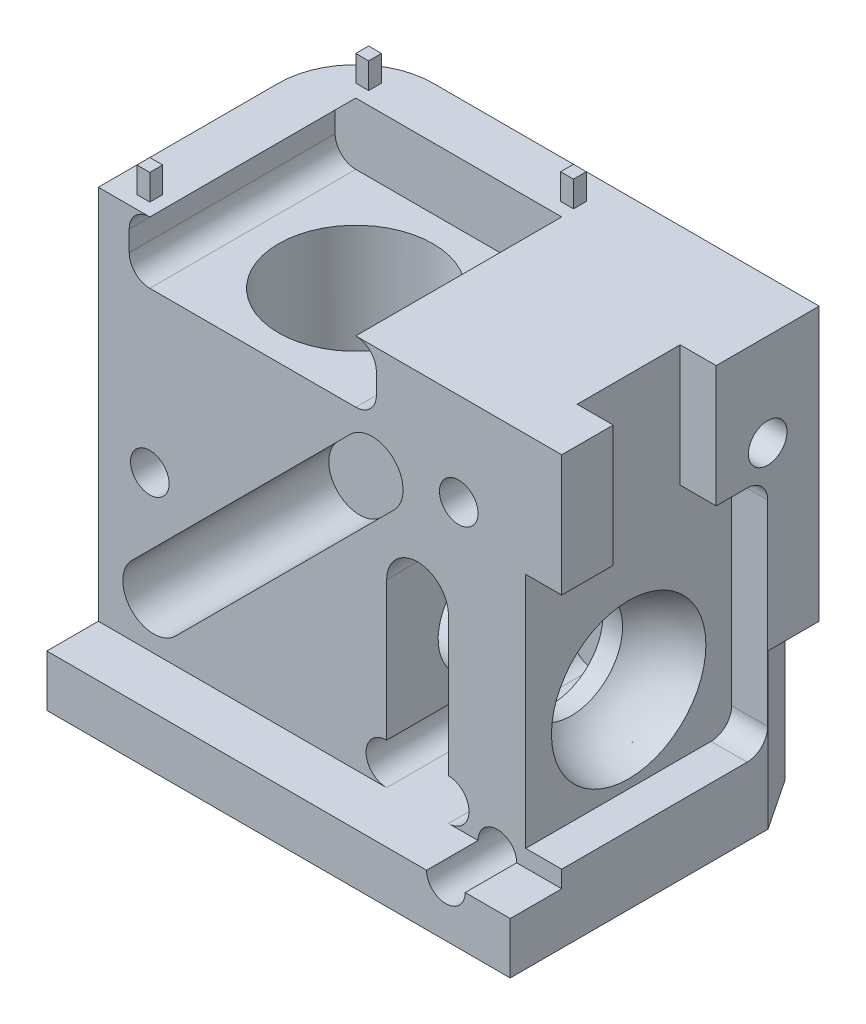
SolidWorks part; units mm, degrees
ref_plane "Front Plane" through (0, 0, 0) normal (0, 0, 1) x (1, 0, 0)
ref_plane "Top Plane" through (0, 0, 0) normal (0, 1, 0) x (1, 0, 0)
ref_plane "Right Plane" through (0, 0, 0) normal (1, 0, 0) x (0, 0, -1)
sketch "Sketch1" plane through (0, 0, 0) normal (0, 1, 0) x (1, 0, 0)
  line L1 (4.5, 3) -> (-4.5, 3)
  line L2 (4.5, 3) -> (4.5, -3)
  line L3 (4.5, -3) -> (-4.5, -3)
  line L4 (-4.5, 3) -> (-4.5, -3)
  line L5 (4.5, 3) -> (-4.5, -3) construction
  line L6 (4.5, -3) -> (-4.5, 3) construction
  point P0 (0, 0)
  dimension "D1" = 6
  dimension "D2" = 9
extrude "Main Body Ext" add sketch "Sketch1" along normal blind 8.3
sketch "Sketch8" plane through (0, 8.3, 0) normal (0, 1, 0) x (1, 0, 0)
  line L0 (0.25, 3) -> (1.5, 1.75)
  line L1 (0.25, 3) -> (-4.5, 3)
  line L2 (1.5, 1.75) -> (1.5, -3)
  line L3 (1.5, -3) -> (-4.5, -3)
  line L4 (-4.5, 3) -> (-4.5, -3)
  line L5 (0.875, 2.375) -> (-4.5, -3) construction
  line L6 (1.5, -3) -> (-4.5, 3) construction
  line L7 (-4.5, 3) -> (-4.5, -3) construction
  line L8 (0, 0) -> (-1.5, 0) construction
  point P0 (-1.5, 0)
  dimension "D1" = 6
  dimension "D2" = 6
  dimension "D3" = 1.25
  dimension "D4" = 3
extrude "Emission Path Ext" add sketch "Sketch8" along normal blind 9
sketch "Sketch3" plane through (0, 0, 0) normal (0, -1, 0) x (1, 0, 0)
  line L0 (-4.5, -3) -> (-4.5, 3) construction
  line L1 (0, 0) -> (-1.5, 0) construction
  circle A0 centre (-1.5, 0) radius 1.25
  dimension "D1" = 3
  dimension "D2" = 2.5
extrude "Emission and Grin Cut" cut sketch "Sketch3" against normal through all
sketch "Sketch4" plane through (4.5, 0, 0) normal (1, 0, 0) x (0, 0, -1)
  line L1 (-3, 0) -> (3, 0) construction
  circle A0 centre (0, 3) radius 1
  dimension "D1" = 2
  dimension "D2" = 3
extrude "Drum Lens Cut" cut sketch "Sketch4" against normal offset from surface (7 mm away) 2 up to face at (-4.5, 8.65, 0)
sketch "Sketch5" plane through (0, 0, 3) normal (0, 0, 1) x (1, 0, 0)
  line L0 (-4.5, 0) -> (4.5, 0) construction
  line L1 (4.5, 8.3) -> (-4.5, 8.3)
  line L2 (4.5, 8.3) -> (4.5, 1)
  line L3 (4.5, 1) -> (-4.5, 1)
  line L4 (-4.5, 8.3) -> (-4.5, 1)
  line L5 (4.5, 8.3) -> (-4.5, 1) construction
  line L6 (4.5, 1) -> (-4.5, 8.3) construction
  line L7 (1.5, 8.3) -> (4.5, 8.3) construction
  line L9 (4.5, 8.3) -> (4.5, 0) construction
  line L10 (-4.5, 17.3) -> (-4.5, 0) construction
  point P0 (0, 4.65)
  dimension "D1" = 1
extrude "FilterSet Cut1" cut sketch "Sketch5" against normal blind 1
sketch "Sketch6" plane through (0, 0, 2) normal (0, 0, 1) x (1, 0, 0)
  line L0 (2.3, 4.5) -> (2.3, 1.8)
  line L1 (1.1, 4.5) -> (2.3, 4.5) construction
  line L2 (2.3, 1) -> (1.1, 1)
  line L3 (-4.5, 1) -> (4.5, 1) construction
  line L4 (-4.5, 8.3) -> (-4.5, 1) construction
  line L5 (-3.9, 7.9) -> (-3.9, 7.5)
  line L6 (1.1, 4.5) -> (1.1, 1.8)
  line L7 (1.5, 8.3) -> (-4.5, 8.3) construction
  line L8 (0.9, 7.9) -> (0.9, 7.5)
  line L9 (-3, 1.5) -> (-3, 1) construction
  line L10 (0.5, 8.3) -> (-3.5, 8.3)
  line L11 (-1.5, 3) -> (-1.5, 1) construction
  line L12 (-1.5, 3) -> (0.4851, 3) construction
  line L13 (0.5, 7.1) -> (-3.5, 7.1)
  line L15 (0.5, 8.3) -> (-3.5, 7.1) construction
  line L16 (0.5, 7.1) -> (-3.5, 8.3) construction
  line L17 (1.1, 1.8) -> (2.3, 1.8) construction
  line L18 (0.3941, 6.5912) -> (-3.8485, 2.3485)
  line L19 (4.5, 1) -> (4.5, 8.3) construction
  line L20 (1.2426, 5.7426) -> (-3, 1.5)
  line L21 (0.3941, 6.5912) -> (-3, 1.5) construction
  line L22 (-3.8485, 2.3485) -> (1.2426, 5.7426) construction
  line L33 (0.5, 8.3) -> (1.102, 8.3) construction
  line L34 (1.102, 8.3) -> (1.102, 7.1) construction
  line L35 (1.102, 7.1) -> (0.5, 7.1) construction
  line L36 (-3.5, 7.1) -> (-4.098, 7.1) construction
  line L37 (-4.098, 7.1) -> (-4.098, 8.3) construction
  line L38 (-4.098, 8.3) -> (-3.5, 8.3) construction
  line L39 (-3.5, 8.3) -> (-2.7284, 6.992) construction
  arc A0 (0.5, 8.3) -> (0.9, 7.9) centre (0.5, 7.9) cw
  arc A1 (1.1, 4.5) -> (2.3, 4.5) centre (1.7, 4.5) cw
  arc A2 (-3.5, 8.3) -> (-3.9, 7.9) centre (-3.5, 7.9) ccw
  arc A3 (0.3941, 6.5912) -> (1.2426, 5.7426) centre (0.8184, 6.1669) cw
  arc A4 (1.1, 1) -> (1.1, 1.8) centre (1.1, 1.4) cw
  arc A5 (-3.8485, 2.3485) -> (-3, 1.5) centre (-3.4243, 1.9243) ccw
  arc A6 (2.3, 1) -> (2.3, 1.8) centre (2.3, 1.4) ccw
  arc A7 (-3.5, 7.1) -> (-3.9, 7.5) centre (-3.5, 7.5) cw
  arc A8 (0.5, 7.1) -> (0.9, 7.5) centre (0.5, 7.5) ccw
  point P5 (-1.5, 7.7)
  point P10 (-1.3029, 4.0456)
  dimension "D10" = 0.5
  dimension "D5" = 2.2
  dimension "D8" = 0.4
  dimension "D11" = 0.4
  dimension "D12" = 0.4
  dimension "D1" = 1.2
  dimension "D2" = 45
  dimension "D3" = 3.5
  dimension "D4" = 1.2
  dimension "D6" = 2
  dimension "D7" = 4
  dimension "D9" = 3
  dimension "D13" = 1.2
  dimension "D14" = 3
  dimension "D15" = 6
extrude "FilterSet Cut2" cut sketch "Sketch6" against normal offset from surface (4 mm away) 1 up to face at (0.4375, 9.2833, -3)
sketch "Sketch10" plane through (0, 17.3, 0) normal (0, 1, 0) x (1, 0, 0)
  line L0 (-1.5, 0) -> (-1.5, -3) construction
  line L1 (-4.5, -3) -> (1.5, -3) construction
  line L3 (-1.5, 0) -> (-4.5, 0) construction
  line L4 (-4.5, 3) -> (-4.5, -3) construction
  circle A0 centre (-1.5, 0) radius 2.5
  dimension "D1" = 5
extrude "Emission Lens Cut" cut sketch "Sketch10" against normal offset from surface (8.5 mm away) 0.5 up to face at (-1.125, 8.3, 1.3125)
sketch "Sketch12" plane through (4.5, 0, 0) normal (1, 0, 0) x (0, 0, -1)
  line L0 (0, 3.635) -> (0, 0) construction
  line L1 (1.6, 5.94) -> (-1.6, 5.94)
  line L2 (1.6, 5.94) -> (1.6, 1.33) construction
  line L3 (-2, 1.33) -> (1.6, 1.33)
  line L4 (-1.6, 5.94) -> (-1.6, 1.33) construction
  line L5 (1.6, 5.94) -> (-1.6, 1.33) construction
  line L6 (1.6, 1.33) -> (-1.6, 5.94) construction
  line L7 (-3, 0) -> (3, 0) construction
  line L9 (-1.6, 5.94) -> (-2, 5.94)
  line L10 (-2, 1) -> (-2, 8.3) construction
  line L11 (-2, 5.94) -> (-2, 1.33)
  line L12 (2, 5.54) -> (2, 1.73)
  arc A1 (1.6, 5.94) -> (2, 5.54) centre (1.6, 5.54) cw
  arc A2 (1.6, 1.33) -> (2, 1.73) centre (1.6, 1.73) ccw
  circle A3 centre (0, 3) radius 1 construction
  point P0 (0, 3.635)
  dimension "D2" = 4.61
  dimension "D3" = 1.67
  dimension "D1" = 3.2
  dimension "D4" = 0.4
sketch "Sketch15" plane through (0, 0, 0) normal (0, -1, 0) x (1, 0, 0)
  line L0 (-3.25, 1.875) -> (-3.25, -1.875) construction
  line L2 (1.5, 0) -> (-1.5, 0) construction
  line L3 (-1.5, 0) -> (-3.25, 0) construction
  circle A0 centre (-3.25, -1.875) radius 0.795
  circle A1 centre (-3.25, 1.875) radius 0.795
  circle A2 centre (1.5, 0) radius 0.795
  dimension "D4" = 1.59
  dimension "D1" = 3.75
  dimension "D2" = 3
  dimension "D3" = 1.75
extrude "Magnets Cut" cut sketch "Sketch15" against normal blind 0.9
sketch "Sketch18" plane through (0, 0, 2) normal (0, 0, 1) x (1, 0, 0)
  line L0 (-4.5, 8.3) -> (-4.5, 1) construction
  line L1 (4.5, 1) -> (4.5, 8.3) construction
  line L2 (4.5, 8.3) -> (1.5, 8.3) construction
  line L3 (-4.5, 0) -> (4.5, 0) construction
  line L7 (-4.5, 1) -> (1.1, 1) construction
  line L9 (-4.5, 1) -> (-4.5, 0) construction
  circle A0 centre (-3.5, 4) radius 0.375
  circle A1 centre (2.5, 6.5) radius 0.375
  circle A2 centre (3.25, 1) radius 0.375
  dimension "D1" = 0.75
  dimension "D2" = 1
  dimension "D3" = 1.8
  dimension "D4" = 2
  dimension "D5" = 3
  dimension "D6" = 1
  dimension "D7" = 7.75
extrude "Screw Holes Cut" cut sketch "Sketch18" against normal blind 3 and the other way through all
fillet "External Fillet 1" radius 1.5 2 edges at (-4.5, 8.65, -3)
sketch "Sketch14" plane through (0, 0, 0) normal (0, -1, 0) x (1, 0, 0)
  line L0 (4.5, -3) -> (4.5, -2.0067)
  line L1 (4.5, 3) -> (4.5, -3) construction
  line L2 (4.5, -2.0067) -> (3.8378, -3)
  line L3 (4.5, -3) -> (-3, -3) construction
  line L4 (3.8378, -3) -> (4.5, -3)
  line L5 (4.5, -3) -> (-4.5, 3) construction
  line L6 (-4.5, -1.5) -> (-4.5, 3) construction
  line L7 (-4.5, 3) -> (4.5, 3) construction
  dimension "D1" = 1.1938
sketch "Sketch28" plane through (0, 7.1, 0) normal (0, 1, 0) x (1, 0, 0)
  circle A0 centre (-1.5, 0) radius 1.5
  dimension "D1" = 3
extrude "Cut-Extrude8" cut sketch "Sketch28" against normal blind 4 and the other way through all
extrude "Cut-Extrude9" cut sketch "Sketch14" against normal blind 3
extrude "Cut-Extrude10" cut sketch "Sketch12" against normal blind 0.7
sketch "Sketch29" plane through (4.5, 0, 0) normal (1, 0, 0) x (0, 0, -1)
  line L0 (3, 8.3) -> (3, 3) construction
  line L1 (-2, 8.3) -> (3, 8.3) construction
  circle A0 centre (2, 6.5) radius 0.375
  dimension "D1" = 0.75
  dimension "D2" = 1
  dimension "D3" = 1.8
extrude "Cut-Extrude11" cut sketch "Sketch29" against normal blind 2.5
sketch "Sketch31" plane through (3.8, 0, 0) normal (1, 0, 0) x (0, 0, -1)
  circle A0 centre (0, 3) radius 1.6
  dimension "D1" = 3.2
sketch "Sketch32" plane through (4.5, 0, 0) normal (1, 0, 0) x (0, 0, -1)
  line L0 (-2, 8.3) -> (3, 8.3) construction
  line L1 (-1, 8.3) -> (1, 8.3)
  line L2 (-1, 8.3) -> (-1, 5.94)
  line L3 (-1, 5.94) -> (1, 5.94)
  line L4 (1, 8.3) -> (1, 5.94)
  line L5 (1.6, 5.94) -> (-2, 5.94) construction
  line L6 (-2, 5.94) -> (-2, 8.3) construction
  line L8 (3, 8.3) -> (3, 3) construction
  dimension "D1" = 1
  dimension "D2" = 2
extrude "Cut-Extrude14" cut sketch "Sketch32" against normal up to surface (0.7 mm away) up to face at (3.8, 3.635, -0.5609)
sketch "Sketch33" plane through (0, 0, 0) normal (0, 0, 1) x (1, 0, 0)
  line L0 (3.8, 3) -> (2.3, 3)
  line L1 (3.8, 1.4) -> (3.8, 4.6) construction
  line L2 (3.8, 3) -> (3.8, 4.5)
  arc A0 (2.3, 3) -> (3.8, 4.5) centre (3.8, 3) cw
  dimension "D2" = 1.5
revolve "Cut-Revolve1" cut sketch "Sketch33" angle 360 about L0
sketch "Sketch36" plane through (0, 17.3, 0) normal (0, 1, 0) x (1, 0, 0)
  line L0 (-4.5, -1.5) -> (-4.5, -3)
  line L1 (-4.5, 1.5) -> (-4.5, -3) construction
  line L2 (-4.5, -3) -> (-3, -3)
  line L3 (-4.5, -3) -> (0, -3) construction
  arc A0 (-4.5, -1.5) -> (-3, -3) centre (-3, -1.5) ccw
  dimension "D1" = 1.5
  dimension "D2" = 1.5
extrude "Cut-Extrude16" cut sketch "Sketch36" against normal up to surface (9 mm away)
sketch "Sketch37" plane through (0, 8.8, 0) normal (0, 1, 0) x (1, 0, 0)
  circle A0 centre (-1.5, 0) radius 2
  circle A1 centre (-1.5, 0) radius 1.5 construction
  dimension "D1" = 4
extrude "Cut-Extrude17" cut sketch "Sketch37" against normal up to next
sketch "Sketch38" plane through (0, 17.3, 0) normal (0, 1, 0) x (1, 0, 0)
  line L0 (-4.375, -1.5) -> (-4.375, 1.5)
  line L1 (1.375, 1.75) -> (1.375, -1.5)
  line L2 (-3, -2.875) -> (0, -2.875)
  line L3 (1.375, 1.75) -> (0.25, 2.875)
  line L4 (0.25, 2.875) -> (-3, 2.875)
  line L5 (0.25, 3) -> (-3, 3) construction
  line L6 (-4.5, 1.5) -> (-4.5, -1.5) construction
  line L7 (-3, -3) -> (0, -3) construction
  line L8 (1.5, -1.5) -> (1.5, 1.75) construction
  line L9 (1.5, 1.75) -> (0.25, 3) construction
  line L10 (-3, 3) -> (0.25, 3)
  line L11 (0.25, 3) -> (1.5, 1.75)
  line L12 (1.5, 1.75) -> (1.5, -1.5)
  line L13 (0, -3) -> (-3, -3)
  line L14 (-4.5, -1.5) -> (-4.5, 1.5)
  arc A0 (1.375, -1.5) -> (0, -2.875) centre (0, -1.5) cw
  arc A1 (-3, 2.875) -> (-4.375, 1.5) centre (-2.8798, 1.3798) ccw
  arc A2 (-3, -2.875) -> (-4.375, -1.5) centre (-3, -1.5) cw
  arc A3 (-4.5, -1.5) -> (-3, -3) centre (-3, -1.5) ccw construction
  arc A4 (0, -3) -> (1.5, -1.5) centre (0, -1.5) ccw construction
  arc A5 (-4.5, 1.5) -> (-3, 3) centre (-3, 1.5) cw
  arc A6 (1.5, -1.5) -> (0, -3) centre (0, -1.5) cw
  arc A7 (-3, -3) -> (-4.5, -1.5) centre (-3, -1.5) cw
  dimension "D2" = 1.5
  dimension "D1" = 0.125
extrude "Cut-Extrude18" cut sketch "Sketch38" against normal up to surface (9 mm away) contours A2 L0 A1 L4 L3 L1 A0 L2 | A7 L14 A5 L10 L11 L12 A6 L13 up to face at (3.3036, 8.3, 0.0004)
sketch "Sketch39" plane through (0, 0, 0) normal (0, 0, 1) x (1, 0, 0)
  line L0 (-4.5, 8.3) -> (-4.2809, 8.3) construction
  line L1 (1.375, 17.3) -> (-4.3904, 17.3)
  line L2 (1.375, 17.3) -> (1.375, 8.3)
  line L3 (1.375, 8.3) -> (-4.3904, 8.3)
  line L4 (-4.3904, 17.3) -> (-4.3904, 8.3)
extrude "Cut-Extrude19" cut sketch "Sketch39" against normal up to surface and the other way up to surface up to face at (-1.375, 12.8, -2.875) other way up to face at (-1.5, 12.8, 2.875)
sketch "Sketch40" plane through (0, 8.3, 0) normal (0, 1, 0) x (1, 0, 0)
  line L0 (-4.5, -2) -> (-4.5, 1.5) construction
  line L1 (-3.75, 2.5) -> (-3.5, 2.5)
  line L2 (-3.75, 2.5) -> (-3.75, 2.25)
  line L3 (-3.75, 2.25) -> (-3.5, 2.25)
  line L4 (-3.5, 2.5) -> (-3.5, 2.25)
  line L5 (0.2281, 2.5) -> (0.4781, 2.5)
  line L6 (0.2281, 2.5) -> (0.2281, 2.25)
  line L7 (0.2281, 2.25) -> (0.4781, 2.25)
  line L8 (0.4781, 2.5) -> (0.4781, 2.25)
  line L9 (-4, -1.75) -> (-3.75, -1.75)
  line L10 (-4, -1.75) -> (-4, -1.5)
  line L11 (-4, -1.5) -> (-3.75, -1.5)
  line L12 (-3.75, -1.75) -> (-3.75, -1.5)
  line L13 (-4.5, -2) -> (1.1, -2) construction
  line L14 (4.5, 3) -> (-3, 3) construction
  point P18 (0.3531, 2.5)
  dimension "D1" = 0.5
  dimension "D2" = 0.5
  dimension "D3" = 0.25
  dimension "D4" = 0.25
  dimension "D5" = 0.25
  dimension "D6" = 0.5
  dimension "D7" = 0.75
  dimension "D8" = 0.5
extrude "Boss-Extrude1" add sketch "Sketch40" along normal blind 0.5
